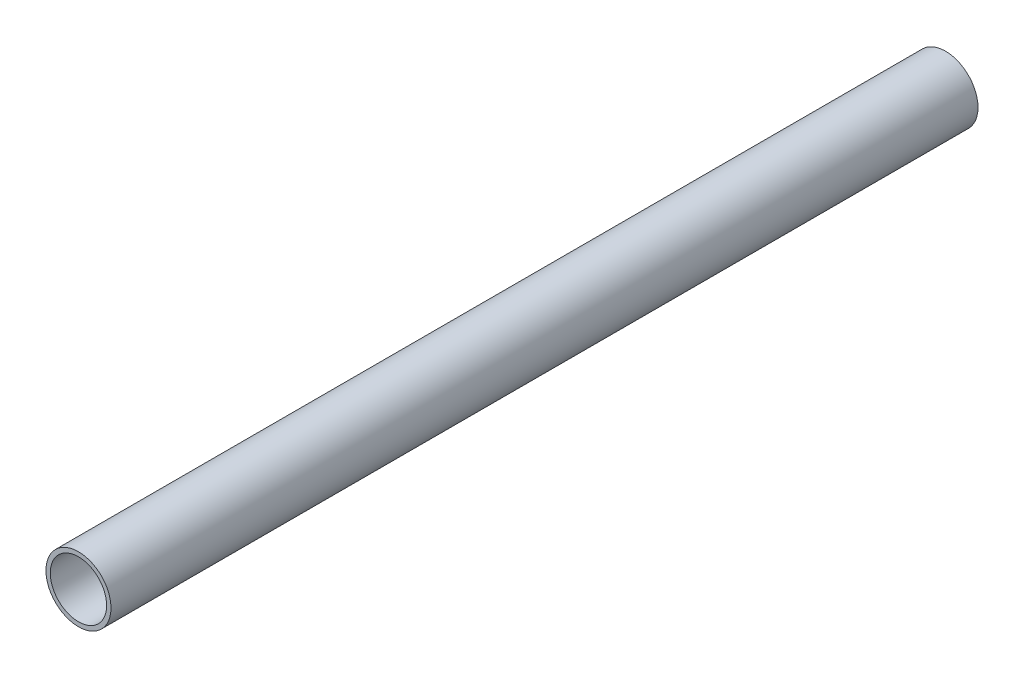
SolidWorks part; units mm, degrees
ref_plane "Front Plane" through (0, 0, 0) normal (0, 0, 1) x (1, 0, 0)
ref_plane "Top Plane" through (0, 0, 0) normal (0, 1, 0) x (1, 0, 0)
ref_plane "Right Plane" through (0, 0, 0) normal (1, 0, 0) x (0, 0, -1)
sketch "Sketch1" plane through (0, 0, 0) normal (0, 0, 1) x (1, 0, 0)
  circle A1 centre (0, 0) radius 15
  circle A2 centre (0, 0) radius 13
  dimension "D1" = 30
  dimension "D2" = 26
extrude "Boss-Extrude1" add sketch "Sketch1" along normal blind 200 and the other way blind 200
